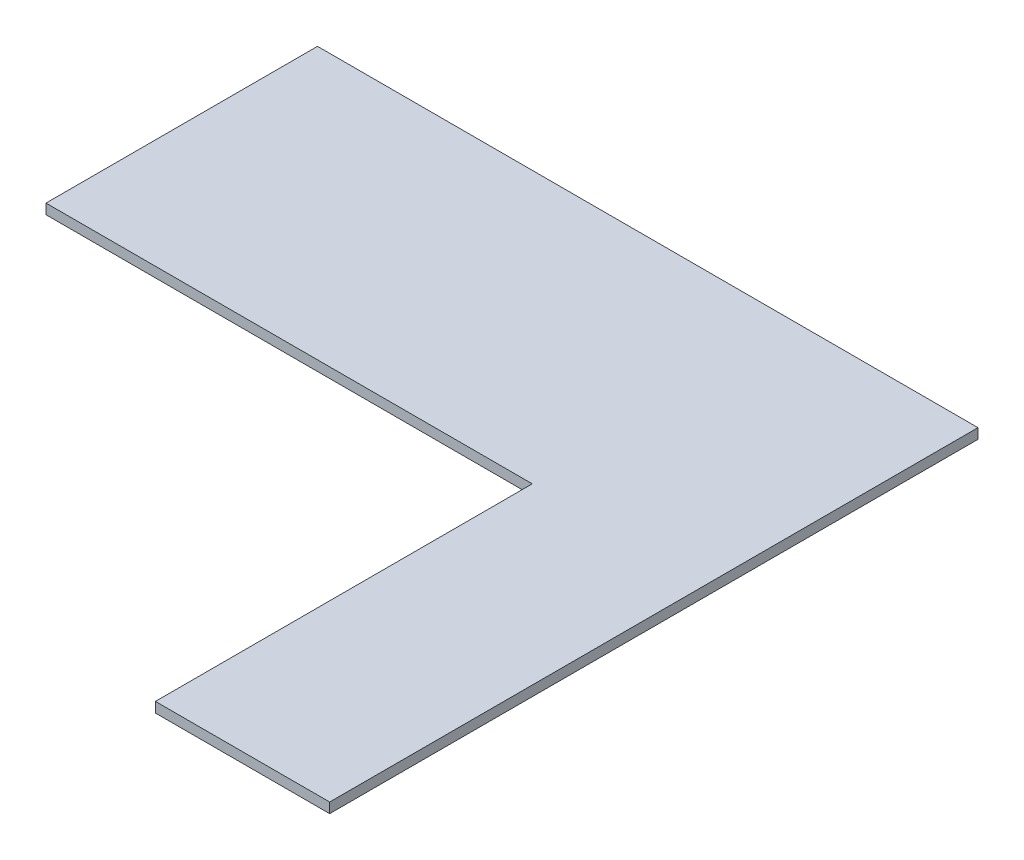
SolidWorks part; units mm, degrees
ref_plane "Спереди" through (0, 0, 0) normal (0, 0, 1) x (1, 0, 0)
ref_plane "Сверху" through (0, 0, 0) normal (0, 1, 0) x (1, 0, 0)
ref_plane "Справа" through (0, 0, 0) normal (1, 0, 0) x (0, 0, -1)
sketch "Эскиз1" plane through (0, 0, 0) normal (0, 1, 0) x (1, 0, 0)
  line L0 (0, 0) -> (0, 670)
  line L1 (0, 670) -> (1630, 670)
  line L2 (1630, 670) -> (1630, -930)
  line L3 (1630, -930) -> (1200, -930)
  line L4 (1200, -930) -> (1200, 0)
  line L5 (1200, 0) -> (0, 0)
extrude "Бобышка-Вытянуть1" add sketch "Эскиз1" along normal blind 25
